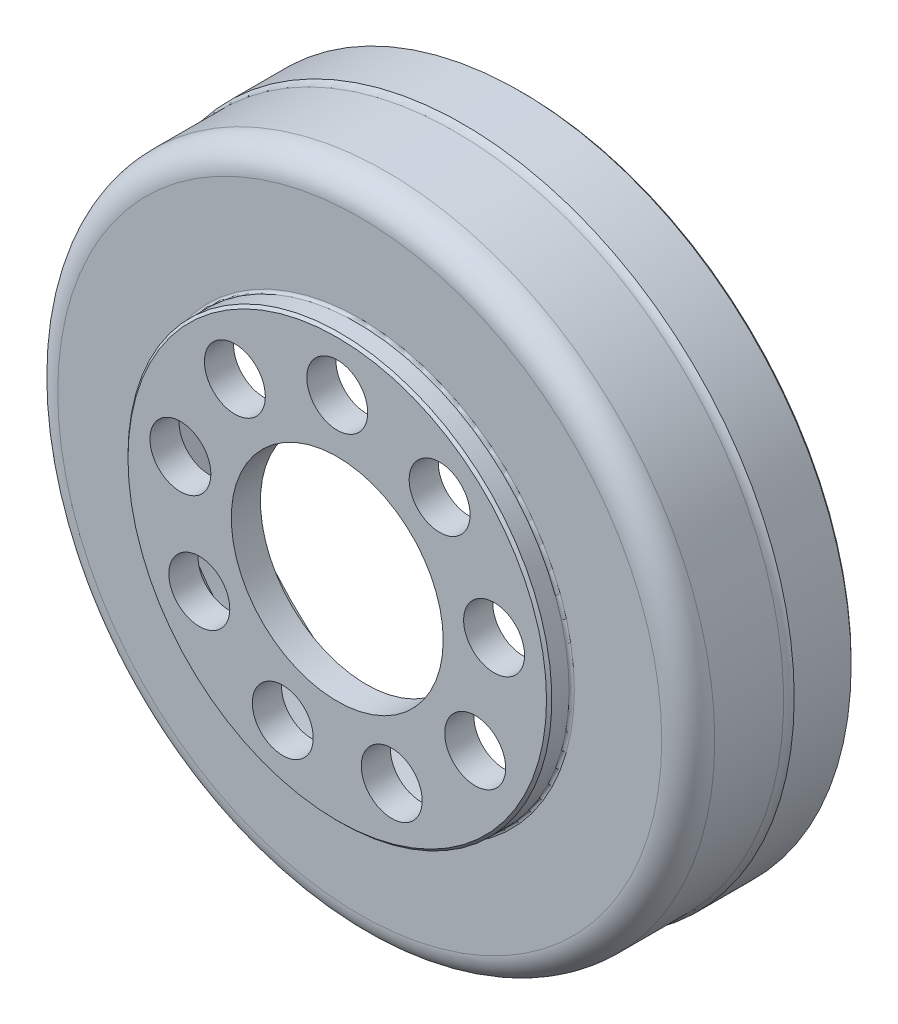
SolidWorks part; units mm, degrees
material "Plain Carbon Steel"
ref_plane "Front Plane" through (0, 0, 0) normal (0, 0, 1) x (1, 0, 0)
ref_plane "Top Plane" through (0, 0, 0) normal (0, 1, 0) x (1, 0, 0)
ref_plane "Right Plane" through (0, 0, 0) normal (1, 0, 0) x (0, 0, -1)
sketch "Sketch1" plane through (0, 0, 0) normal (0, 0, 1) x (1, 0, 0)
  circle A0 centre (0, 0) radius 25
  dimension "D1" = 50
extrude "Boss-Extrude1" add sketch "Sketch1" along normal blind 4.5
sketch "Sketch2" plane through (0, 0, 4.5) normal (0, 0, 1) x (1, 0, 0)
  circle A0 centre (0, 0) radius 24.8
  dimension "D1" = 49.6
extrude "Boss-Extrude2" add sketch "Sketch2" along normal blind 7.8
fillet "Fillet1" radius 2 1 edges at (24.8, 0, 12.3)
fillet "Fillet2" radius 1 1 edges at (24.8, 0, 4.5)
shell "Shell1" thickness 0.5 removed face at (25, 0, 0)
chamfer "Chamfer1" distance 0.2 angle 45 1 edges at (25, 0, 0)
sketch "Sketch3" plane through (0, 0, 12.3) normal (0, 0, 1) x (1, 0, 0)
  circle A0 centre (0, 0) radius 16
  dimension "D1" = 32
extrude "Boss-Extrude3" add sketch "Sketch3" along normal blind 1.7
chamfer "Chamfer2" distance 0.2 angle 45 1 edges at (16, 0, 14)
fillet "Fillet3" radius 0.2 1 edges at (16, 0, 12.3)
sketch "Sketch4" plane through (0, 0, 14) normal (0, 0, 1) x (1, 0, 0)
  line L0 (0, 12.0247) -> (0, 0) construction
  circle A0 centre (0, 0) radius 8
  circle A1 centre (0, 12.0247) radius 2.3
  circle A10 centre (7.7293, 9.2114) radius 2.3
  circle A11 centre (11.842, 2.0881) radius 2.3
  circle A12 centre (10.4137, -6.0123) radius 2.3
  circle A13 centre (4.1127, -11.2995) radius 2.3
  circle A14 centre (-4.1127, -11.2995) radius 2.3
  circle A15 centre (-10.4137, -6.0123) radius 2.3
  circle A16 centre (-11.842, 2.0881) radius 2.3
  circle A17 centre (-7.7293, 9.2114) radius 2.3
  point P23 (0, 0)
  point P24 (0, 0)
  dimension "D1" = 16
  dimension "D2" = 4.6
  dimension "D3" = 12.0247
  dimension "D4" = 9
extrude "Cut-Extrude1" cut sketch "Sketch4" against normal through all
